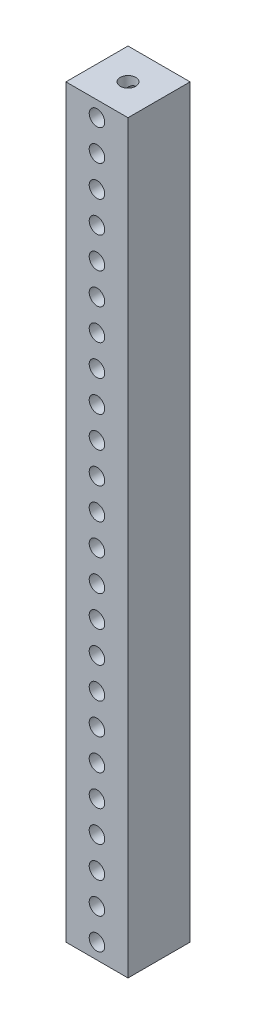
SolidWorks part; units mm, degrees
ref_plane "Front Plane" through (0, 0, 0) normal (0, 0, 1) x (1, 0, 0)
ref_plane "Top Plane" through (0, 0, 0) normal (0, 1, 0) x (1, 0, 0)
ref_plane "Right Plane" through (0, 0, 0) normal (1, 0, 0) x (0, 0, -1)
sketch "Sketch1" plane through (0, 0, 0) normal (0, 1, 0) x (1, 0, 0)
  line L1 (-10, -10) -> (10, -10)
  line L2 (-10, -10) -> (-10, 10)
  line L3 (-10, 10) -> (10, 10)
  line L4 (10, -10) -> (10, 10)
  line L5 (-10, -10) -> (10, 10) construction
  line L6 (-10, 10) -> (10, -10) construction
  circle A0 centre (0, 0) radius 2.5
  point P0 (0, 0)
  dimension "D3" = 5
  dimension "D1" = 20
  dimension "D2" = 20
extrude "Boss-Extrude1" add sketch "Sketch1" along normal blind 240
sketch "Sketch2" plane through (0, 0, 10) normal (0, 0, 1) x (1, 0, 0)
  circle A0 centre (0, 5) radius 2.5
  dimension "D1" = 5
  dimension "D2" = 5
extrude "Cut-Extrude1" cut sketch "Sketch2" against normal blind 100
pattern_linear "LPattern1" count 22 spacing 10 along (0, 1, 0) of "Cut-Extrude1"
sketch "Sketch3" plane through (0, 0, 10) normal (0, 0, 1) x (1, 0, 0)
  line L0 (0, -760) -> (0, 49240) construction
  line L1 (-10, 240) -> (10, 240) construction
  circle A0 centre (0, 235) radius 2.5
  circle A1 centre (0, 225) radius 2.5
  point P5 (0, 240)
  dimension "D1" = 5
  dimension "D2" = 5
  dimension "D3" = 5
  dimension "D4" = 15
extrude "Cut-Extrude2" cut sketch "Sketch3" against normal through all
